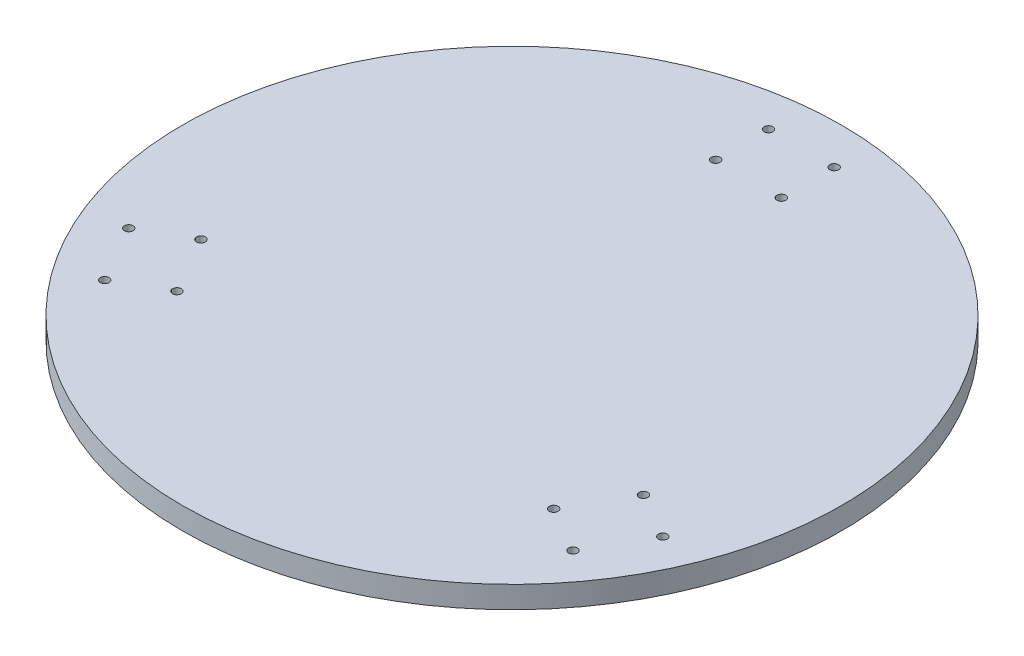
SolidWorks part; units mm, degrees
material "Acrylic"
ref_plane "Front Plane" through (0, 0, 0) normal (0, 0, 1) x (1, 0, 0)
ref_plane "Top Plane" through (0, 0, 0) normal (0, 1, 0) x (1, 0, 0)
ref_plane "Right Plane" through (0, 0, 0) normal (1, 0, 0) x (0, 0, -1)
sketch "Sketch1" plane through (0, 0, 0) normal (0, 1, 0) x (1, 0, 0)
  circle A0 centre (0, 0) radius 150
  dimension "D1" = 300
extrude "Boss-Extrude1" add sketch "Sketch1" along normal blind 10
sketch "Sketch2" plane through (0, 10, 0) normal (0, 1, 0) x (1, 0, 0)
  line L0 (0, 0) -> (0, 174.2635) construction
  circle A0 centre (-14.95, 131.71) radius 2
  circle A1 centre (-14.95, 107.65) radius 2
  circle A2 centre (14.95, 131.71) radius 2
  circle A3 centre (14.95, 107.65) radius 2
  circle A4 centre (121.5392, -52.9079) radius 2
  circle A5 centre (106.5892, -78.8021) radius 2
  circle A6 centre (100.7026, -40.8779) radius 2
  circle A7 centre (85.7526, -66.7721) radius 2
  circle A8 centre (-106.5892, -78.8021) radius 2
  circle A9 centre (-121.5392, -52.9079) radius 2
  circle A10 centre (-85.7526, -66.7721) radius 2
  circle A11 centre (-100.7026, -40.8779) radius 2
  point P30 (0, 0)
  dimension "D1" = 4
  dimension "D5" = 131.71
  dimension "D2" = 29.9
  dimension "D3" = 14.95
  dimension "D4" = 24.06
  dimension "D6" = 3
extrude "Cut-Extrude2" cut sketch "Sketch2" against normal blind 10
ref_axis "Axis1" through (14.95, 0, -131.71) along (0, 1, 0)
ref_axis "Axis2" through (-14.95, 0, -131.71) along (0, 1, 0)
ref_axis "Axis3" through (14.95, 0, -107.65) along (0, 1, 0)
ref_axis "Axis4" through (-14.95, 0, -107.65) along (0, 1, 0)
ref_axis "Axis5" through (100.7026, 0, 40.8779) along (0, 1, 0)
ref_axis "Axis6" through (121.5392, 0, 52.9079) along (0, 1, 0)
ref_axis "Axis7" through (85.7526, 0, 66.7721) along (0, 1, 0)
ref_axis "Axis8" through (106.5892, 0, 78.8021) along (0, 1, 0)
ref_axis "Axis9" through (-100.7026, 0, 40.8779) along (0, 1, 0)
ref_axis "Axis10" through (-85.7526, 0, 66.7721) along (0, 1, 0)
ref_axis "Axis11" through (-106.5892, 0, 78.8021) along (0, 1, 0)
ref_axis "Axis12" through (-121.5392, 0, 52.9079) along (0, 1, 0)
